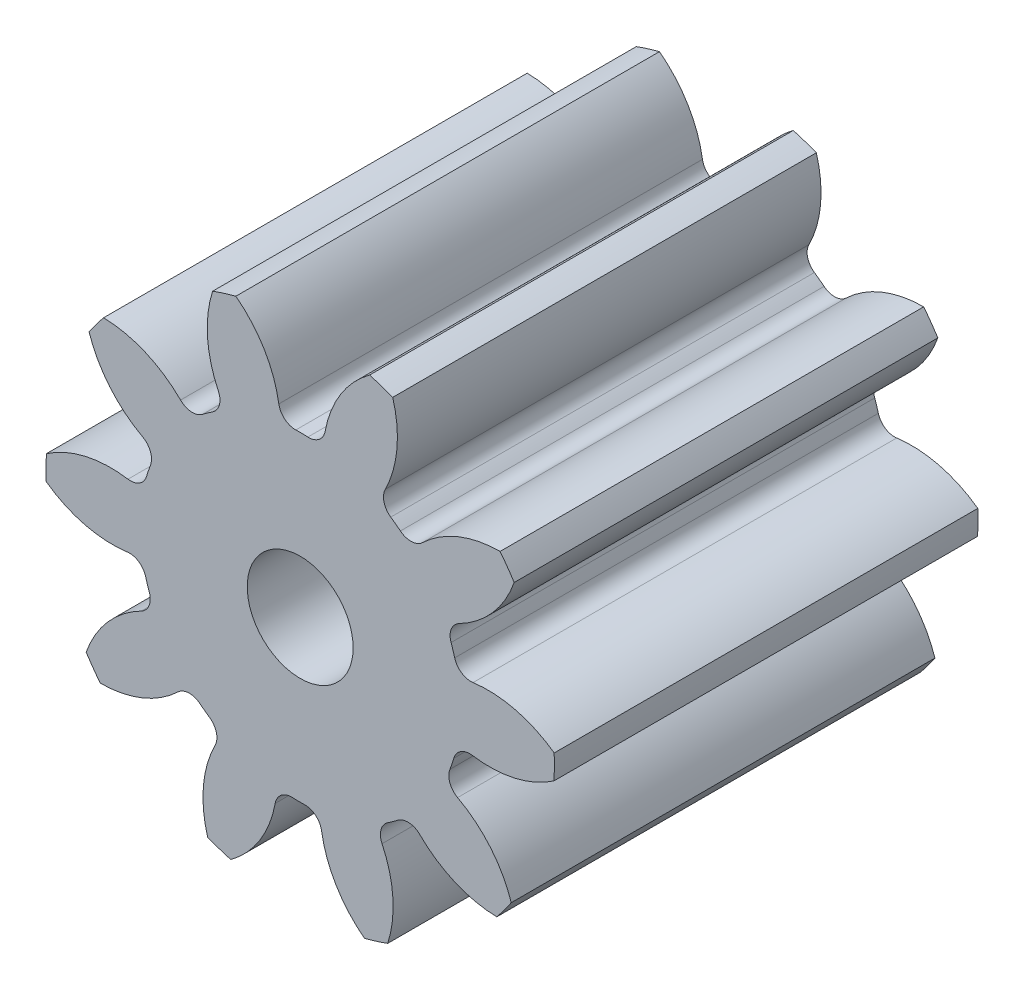
SolidWorks part; units mm, degrees
ref_plane "Front" through (0, 0, 0) normal (0, 0, 1) x (1, 0, 0)
ref_plane "Top" through (0, 0, 0) normal (0, 1, 0) x (1, 0, 0)
ref_plane "Right" through (0, 0, 0) normal (1, 0, 0) x (0, 0, -1)
sketch "Sketch3" plane through (0, 0, 0) normal (0, 0, 1) x (1, 0, 0)
  circle A0 centre (0, 0) radius 15.24
  dimension "od" = 30.48
extrude "gearBody" add sketch "Sketch3" along normal blind 25.4
sketch "Sketch2" plane through (0, 0, 0) normal (0, 0, 1) x (1, 0, 0)
  line L0 (0, 0) -> (11.3595, 4.7053) construction
  line L1 (12.8367, -12.0857) -> (0, 0) construction
  line L2 (0, 0) -> (36.3143, 0) construction
  line L3 (12.544, -1.9847) -> (11.1917, -6.003) construction
  line L5 (11.8678, -3.9939) -> (0, 0) construction
  line L7 (0, 0) -> (12.2955, 0) construction
  arc A0 (12.1241, -2.0456) -> (10.8941, -5.7007) centre (0, 0) ccw construction
  arc A1 (15.214, -0.8896) -> (12.6563, -8.4897) centre (0, 0) ccw construction
  arc A2 (12.544, -1.9847) -> (11.1917, -6.003) centre (0, 0) ccw construction
  arc A3 (8.9781, -3.4023) -> (9.2084, -2.718) centre (0, 0) ccw
  arc A4 (12.8367, -12.0857) -> (9.4391, -4.6417) centre (6.2035, -10.6158) ccw
  arc A5 (12.8367, -12.0857) -> (17.5318, 1.8658) centre (0, 0) ccw
  arc A6 (17.5318, 1.8658) -> (10.3249, -2.0095) centre (11.3595, 4.7053) cw
  arc A7 (9.2084, -2.718) -> (10.3249, -2.0095) centre (10.1719, -3.0024) cw
  arc A8 (9.4391, -4.6417) -> (8.9781, -3.4023) centre (9.9175, -3.7583) cw
  point P6 (17.5318, 1.8658)
  point P22 (12.8367, -12.0857)
  dimension "baseDia" = 24.591
  dimension "od" = 30.48
  dimension "pd" = 25.4
  dimension "rd" = 19.2024
  dimension "rFillet" = 1.0046
  dimension "pointX" = 17.5318
  dimension "pointY" = 1.8658
  dimension "CTT" = 4.0183
  dimension "flankCenterAngle" = 22.5
extrude "toothCut" cut sketch "Sketch2" along normal through all
pattern_circular "CirPattern1" count 10 over 360 about axis through (0, 0, 25.4) along (0, 0, -1) of "toothCut"
ref_axis "toothSpace" through (0, 0, 0) along (0.9478, -0.319, 0)
ref_axis "Axis2" through (12.235, -9.0864, 0) along (-0.8028, 0.5962, 0)
sketch "hub1Dia" plane through (0, 0, 0) normal (0, 0, -1) x (-1, 0, 0)
  circle A0 centre (0, 0) radius 12.7
  dimension "hub1Dia" = 25.4
sketch "hub2Dia" plane through (0, 0, 25.4) normal (0, 0, 1) x (1, 0, 0)
  circle A0 centre (0, 0) radius 12.7
  dimension "hub2dia" = 25.4
sketch "boreDia" plane through (0, 0, 0) normal (0, 0, 1) x (1, 0, 0)
  circle A0 centre (0, 0) radius 3.175
  dimension "boreDia" = 6.35
extrude "bore" cut sketch "boreDia" against normal mid plane 25400
sketch "kwy1sketch" plane through (0, 0, 0) normal (0, 0, 1) x (1, 0, 0)
  line L0 (-4.3738, 2.5866) -> (0, 0) construction
  line L1 (31.0606, -3.6142) -> (18.131, -25.4772)
  line L2 (18.131, -25.4772) -> (-9.1976, -9.3153)
  line L3 (31.0606, -3.6142) -> (3.7319, 12.5477)
  line L4 (-9.1976, -9.3153) -> (0, 0)
  line L5 (0, 0) -> (3.7319, 12.5477)
  line L6 (0, 0) -> (9.0997, -3.0623) construction
  line L7 (24.5958, -14.5457) -> (0, 0) construction
  arc A7 (8.9781, -3.4023) -> (9.2084, -2.718) centre (0, 0) ccw construction
  point P9 (24.5958, -14.5457)
  point P13 (-0.7296, 0.4315)
  dimension "kwy1width" = 25.4
  dimension "kwy1depth" = 28.575
  dimension "kwy1angle" = 12
  dimension "kwy1Depth2" = 31.75
sketch "kwy2sketch" plane through (0, 0, 0) normal (0, 0, 1) x (1, 0, 0)
  line L0 (9.0997, -3.0623) -> (0, 0) construction
  line L1 (0, 0) -> (-3.4011, -0.8733) construction
  line L2 (24.5188, 19.4075) -> (30.8357, -5.1945)
  line L3 (30.8357, -5.1945) -> (0.0832, -13.0906)
  line L4 (24.5188, 19.4075) -> (-6.2337, 11.5114)
  line L5 (0.0832, -13.0906) -> (0, 0)
  line L6 (0, 0) -> (-6.2337, 11.5114)
  arc A2 (8.9781, -3.4023) -> (9.2084, -2.718) centre (0, 0) ccw construction
  point P10 (27.6772, 7.1065)
  dimension "kwy2angle" = 33
  dimension "kwy2Width" = 25.4
  dimension "kwy2depth" = 28.575
  dimension "kwy2Depth2" = 31.75
sketch "kwy3sketch" plane through (0, 0, 0) normal (0, 0, 1) x (1, 0, 0)
  line L0 (9.0997, -3.0623) -> (0, 0) construction
  line L1 (0, 0) -> (-1.2931, -2.1866) construction
  line L2 (3.6142, 31.0606) -> (25.4772, 18.131)
  line L3 (25.4772, 18.131) -> (9.3153, -9.1976)
  line L4 (3.6142, 31.0606) -> (-12.5477, 3.7319)
  line L5 (9.3153, -9.1976) -> (0, 0)
  line L6 (-12.5477, 3.7319) -> (0, 0)
  point P10 (14.5457, 24.5958)
  dimension "kwy3angle" = 78
  dimension "kwy3depth" = 28.575
  dimension "kwy3width" = 25.4
  dimension "kwy3Depth2" = 31.75
sketch "kwy4sketch" plane through (0, 0, 0) normal (0, 0, 1) x (1, 0, 0)
  line L0 (9.0997, -3.0623) -> (0, 0) construction
  line L1 (0, 0) -> (0.494, -1.9239) construction
  line L2 (5.1945, 30.8357) -> (-19.4075, 24.5188)
  line L3 (-19.4075, 24.5188) -> (-11.5114, -6.2337)
  line L4 (-11.5114, -6.2337) -> (0, 0)
  line L5 (13.0906, 0.0832) -> (0, 0)
  line L6 (5.1945, 30.8357) -> (13.0906, 0.0832)
  point P15 (-7.1065, 27.6772)
  dimension "kwy4angle" = 123
  dimension "kwy4depth" = 28.575
  dimension "kwy4width" = 25.4
  dimension "kwy4Depth2" = 31.75
sketch "kwy5sketch" plane through (0, 0, 0) normal (0, 0, 1) x (1, 0, 0)
  line L0 (9.0997, -3.0623) -> (0, 0) construction
  line L1 (0, 0) -> (1.4683, -0.8684) construction
  line L2 (-18.131, 25.4772) -> (-31.0606, 3.6142)
  line L3 (-31.0606, 3.6142) -> (-3.7319, -12.5477)
  line L4 (-18.131, 25.4772) -> (9.1976, 9.3153)
  line L5 (-3.7319, -12.5477) -> (0, 0)
  line L6 (9.1976, 9.3153) -> (0, 0)
  point P10 (-24.5958, 14.5457)
  dimension "kwy5width" = 25.4
  dimension "kwy5depth" = 28.575
  dimension "kwy5angle" = 168
  dimension "kwy5Depth2" = 31.75
sketch "kwy6sketch" plane through (0, 0, 0) normal (0, 0, 1) x (1, 0, 0)
  line L0 (9.0997, -3.0623) -> (0, 0) construction
  line L1 (0, 0) -> (1.651, 0.4239) construction
  line L2 (-30.8357, 5.1945) -> (-24.5188, -19.4075)
  line L3 (-24.5188, -19.4075) -> (6.2337, -11.5114)
  line L4 (-30.8357, 5.1945) -> (-0.0832, 13.0906)
  line L5 (6.2337, -11.5114) -> (0, 0)
  line L6 (-0.0832, 13.0906) -> (0, 0)
  point P10 (-27.6772, -7.1065)
  dimension "kwy6angle" = 213
  dimension "kwy6width" = 25.4
  dimension "kwy6depth" = 28.575
  dimension "kwy6Depth2" = 31.75
sketch "kwy7sketch" plane through (0, 0, 0) normal (0, 0, 1) x (1, 0, 0)
  line L0 (9.0997, -3.0623) -> (0, 0) construction
  line L1 (0, 0) -> (0.9721, 1.6437) construction
  line L2 (-25.4772, -18.131) -> (-3.6142, -31.0606)
  line L3 (-25.4772, -18.131) -> (-9.3153, 9.1976)
  line L4 (-3.6142, -31.0606) -> (12.5477, -3.7319)
  line L5 (-9.3153, 9.1976) -> (0, 0)
  line L6 (12.5477, -3.7319) -> (0, 0)
  point P10 (-14.5457, -24.5958)
  dimension "kwy7angle" = 78
  dimension "kwy7width" = 25.4
  dimension "kwy7depth" = 28.575
  dimension "kwy7angle1" = 258
  dimension "kwy7Depth2" = 31.75
sketch "kwy8sketch" plane through (0, 0, 0) normal (0, 0, 1) x (1, 0, 0)
  line L0 (9.0997, -3.0623) -> (0, 0) construction
  line L1 (0, 0) -> (-0.4219, 1.6433) construction
  line L2 (-5.1945, -30.8357) -> (19.4075, -24.5188)
  line L3 (19.4075, -24.5188) -> (11.5114, 6.2337)
  line L4 (-5.1945, -30.8357) -> (-13.0906, -0.0832)
  line L5 (11.5114, 6.2337) -> (0, 0)
  line L6 (-13.0906, -0.0832) -> (0, 0)
  point P10 (7.1065, -27.6772)
  dimension "kwy8angle" = 303
  dimension "kwy8width" = 25.4
  dimension "kwy8depth" = 28.575
  dimension "kwy8Depth2" = 31.75
sketch "centerLine" plane through (0, 0, 0) normal (0, 1, 0) x (1, 0, 0)
  line L0 (0, 36.4807) -> (0, -59.6309) construction
ref_plane "CB1plane" through (0, 0, 0) normal (0, 0, -1) x (-1, 0, 0)
sketch "CB1diameter" plane through (0, 0, 0) normal (0, 0, -1) x (-1, 0, 0)
  circle A0 centre (0, 0) radius 12.7
  dimension "CB1diameter" = 25.4
ref_plane "CB2plane" through (0, 0, 25.4) normal (0, 0, 1) x (1, 0, 0)
sketch "CB2diameter" plane through (0, 0, 25.4) normal (0, 0, 1) x (1, 0, 0)
  circle A0 centre (0, 0) radius 12.7
  dimension "CB2diameter" = 25.4
ref_axis "Axis1" through (0, 0, 50) along (0, 0, -1)
sketch3d "3DSketch1" plane through (0, 0, 0) normal (0, 0, 1) x (1, 0, 0)
